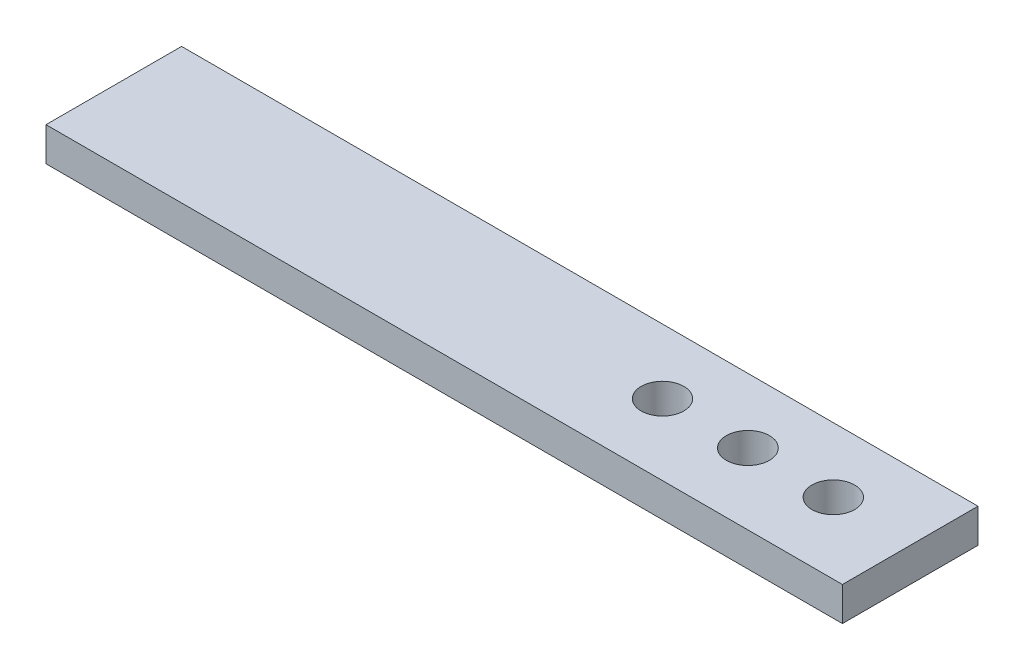
SolidWorks part; units mm, degrees
ref_plane "Front Plane" through (0, 0, 0) normal (0, 0, 1) x (1, 0, 0)
ref_plane "Top Plane" through (0, 0, 0) normal (0, 1, 0) x (1, 0, 0)
ref_plane "Right Plane" through (0, 0, 0) normal (1, 0, 0) x (0, 0, -1)
sketch "Sketch1" plane through (0, 0, 0) normal (0, 1, 0) x (1, 0, 0)
  line L1 (0, 0) -> (100, 0)
  line L2 (0, 0) -> (0, 12.7)
  line L3 (0, 12.7) -> (100, 12.7)
  line L4 (100, 0) -> (100, 12.7)
  circle A0 centre (92.5004, 6.6459) radius 2
  circle A1 centre (84.5004, 6.6459) radius 2.0149
  circle A2 centre (76.5004, 6.6459) radius 2
  dimension "D3" = 4
  dimension "D1" = 100
  dimension "D2" = 12.7
extrude "Boss-Extrude1" add sketch "Sketch1" along normal blind 3.175
sketch "Sketch3" plane through (0, 0, 0) normal (-1, 0, 0) x (0, 0, 1)
  line L1 (-19.1412, -9.156) -> (10.8866, -9.156)
  line L2 (-19.1412, -9.156) -> (-19.1412, 8.1226)
  line L3 (-19.1412, 8.1226) -> (10.8866, 8.1226)
  line L4 (10.8866, -9.156) -> (10.8866, 8.1226)
extrude "Cut-Extrude1" cut sketch "Sketch3" against normal blind 25.4
